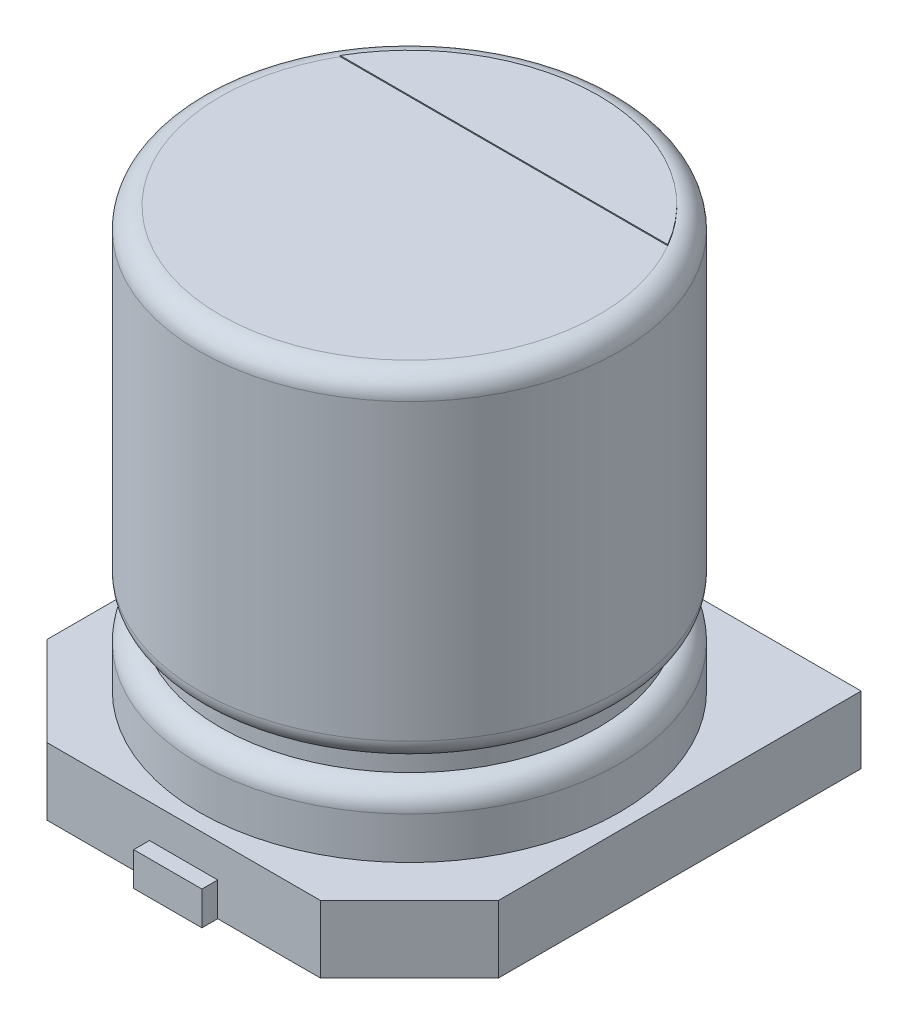
SolidWorks part; units mm, degrees
ref_plane "Front" through (0, 0, 0) normal (0, 0, 1) x (1, 0, 0)
ref_plane "Top" through (0, 0, 0) normal (0, 1, 0) x (1, 0, 0)
ref_plane "Right" through (0, 0, 0) normal (1, 0, 0) x (0, 0, -1)
sketch "Sketch1" plane through (0, 0, 0) normal (0, 0, 1) x (1, 0, 0)
  line L0 (0, 8.0822) -> (0, 0) construction
  line L1 (0, 4) -> (-1.8, 4)
  line L2 (-2, 3.8) -> (-2, 1)
  line L3 (-1.8, 0.8) -> (-1.8, 0.6)
  line L4 (-2, 0.4) -> (-2, 0)
  line L5 (-2, 0) -> (0, 0)
  line L6 (0, 0) -> (0, 4)
  line L7 (0, 0) -> (2.8151, 0) construction
  arc A0 (-1.8, 4) -> (-2, 3.8) centre (-1.8, 3.8) ccw
  arc A1 (-2, 1) -> (-1.8, 0.8) centre (-1.8, 1) ccw
  arc A2 (-1.8, 0.6) -> (-2, 0.4) centre (-1.8, 0.4) ccw
  dimension "D2" = 0.4
  dimension "D3" = 0.2
  dimension "D6" = 0.2
  dimension "D1" = 4
  dimension "D4" = 0.2
  dimension "D5" = 4
revolve "Revolve1" add sketch "Sketch1" angle 360 about L0
sketch "Sketch2" plane through (0, 4, 0) normal (0, 1, 0) x (1, 0, 0)
  line L0 (0, 0) -> (0, 1.8) construction
  line L1 (-1.5588, 0.9) -> (1.5588, 0.9)
  circle A0 centre (0, 0) radius 1.8 construction
  arc A1 (1.5588, 0.9) -> (-1.5588, 0.9) centre (0, 0) ccw
  dimension "D1" = 0.9
extrude "Boss-Extrude1" add sketch "Sketch2" along normal blind 0.01
sketch "Sketch3" plane through (0, 0, 0) normal (0, -1, 0) x (-1, 0, 0)
  line L0 (0, 0.5) -> (0, 0) construction
  line L1 (0, 0) -> (0.9284, 0) construction
  line L28 (1.3015, -2.15) -> (2.15, -1.3015)
  line L29 (2.15, -1.3015) -> (2.15, 2.15)
  line L31 (0.325, 2.15) -> (0.325, 0.5)
  line L32 (0.325, 0.5) -> (-0.325, 0.5)
  line L33 (-0.325, 0.5) -> (-0.325, 2.15)
  line L34 (2.15, 2.15) -> (-2.15, 2.15)
  line L35 (-2.15, 2.15) -> (-2.15, -1.3015)
  line L36 (-2.15, -1.3015) -> (-1.3015, -2.15)
  line L37 (-1.3015, -2.15) -> (1.3015, -2.15)
  line L38 (-0.325, -2.15) -> (-0.325, -0.5)
  line L39 (-0.325, -0.5) -> (0.325, -0.5)
  line L40 (0.325, -0.5) -> (0.325, -2.15)
  circle M43 centre (0, 0) radius 2
  dimension "D1" = 1
  dimension "D2" = 4.3
  dimension "D3" = 4.3
  dimension "D4" = 0.65
  dimension "D5" = 1.2
  dimension "D6" = 45
extrude "Boss-Extrude2" add sketch "Sketch3" along normal blind 0.64 contours L34 L35 L36 L37 L28 L29
extrude "Cut-Extrude1" cut sketch "Sketch3<3>" against normal blind 0.32 from vertex contours L33 L32 L31 M43 | L40 L39 L38 M43 | L31 L34 L33 M43 | L40 L38 L37 M43 region at (0, 0, 2.0704) region at (0, 0, 1.2456) region at (0, 0, -2.0704) region at (0, 0, -1.2456) starting at point (-2.15, -0.64, -2.15)
sketch "Sketch3<3>" plane through (0, 0, 0) normal (0, -1, 0) x (-1, 0, 0) same geometry as "Sketch3"
sketch "Sketch4" plane through (0, -0.32, 0) normal (0, -1, 0) x (1, 0, 0)
  line L0 (0.325, -0.5) -> (0.325, -2.15) construction
  line L1 (-0.325, -0.5) -> (0.325, -0.5)
  line L2 (-0.325, -0.5) -> (-0.325, -2.3)
  line L3 (-0.325, -2.3) -> (0.325, -2.3)
  line L4 (0.325, -0.5) -> (0.325, -2.3)
  line L5 (0, 0) -> (4.1796, 0) construction
  line L6 (-0.325, 0.5) -> (-0.325, 2.3)
  line L7 (-0.325, 0.5) -> (0.325, 0.5)
  line L8 (0.325, 0.5) -> (0.325, 2.3)
  line L9 (-0.325, 2.3) -> (0.325, 2.3)
  dimension "D1" = 1.8
extrude "Boss-Extrude3" add sketch "Sketch4" along normal blind 0.32
split line "Split Line1"
sketch "Sketch4<2>" plane through (0, -0.32, 0) normal (0, -1, 0) x (1, 0, 0) same geometry as "Sketch4"
